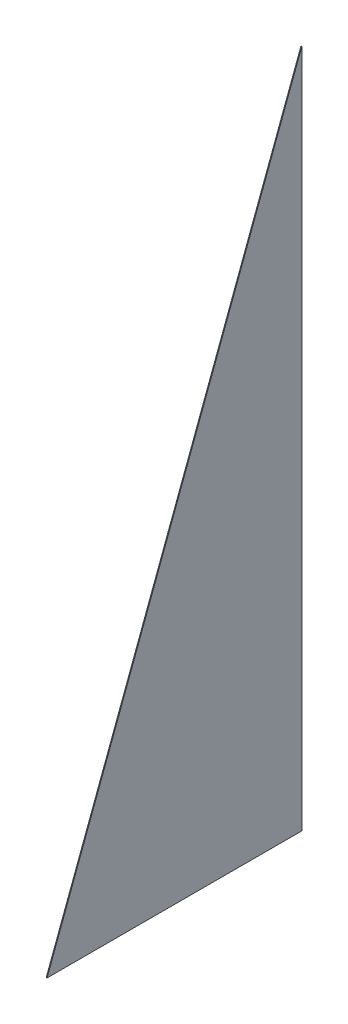
SolidWorks part; units mm, degrees
ref_plane "Front Plane" through (0, 0, 0) normal (0, 0, 1) x (1, 0, 0)
ref_plane "Top Plane" through (0, 0, 0) normal (0, 1, 0) x (1, 0, 0)
ref_plane "Right Plane" through (0, 0, 0) normal (1, 0, 0) x (0, 0, -1)
sketch "Sketch1" plane through (0, 0, 0) normal (1, 0, 0) x (0, 0, -1)
  line L0 (0, 0) -> (0, 800)
  line L1 (0, 800) -> (-300, 0)
  line L2 (-300, 0) -> (0, 0)
  dimension "D1" = 800
  dimension "D2" = 300
extrude "Boss-Extrude1" add sketch "Sketch1" along normal blind 1
